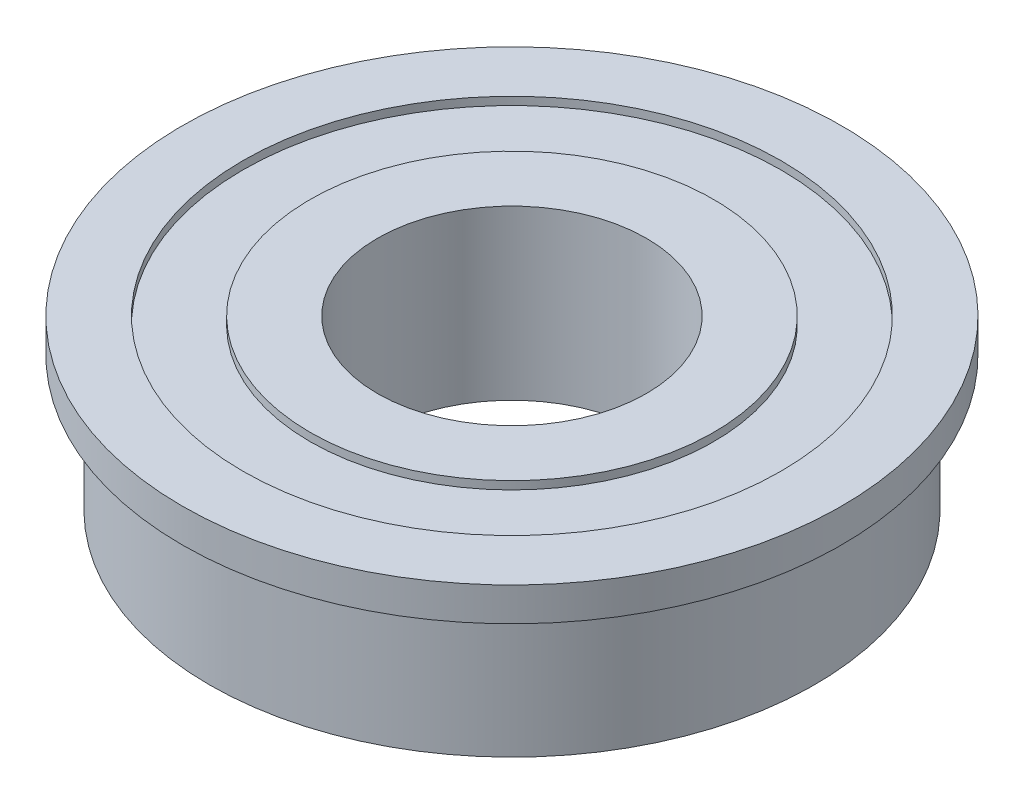
SolidWorks part; units mm, degrees
ref_plane "Front Plane" through (0, 0, 0) normal (0, 0, 1) x (1, 0, 0)
ref_plane "Top Plane" through (0, 0, 0) normal (0, 1, 0) x (1, 0, 0)
ref_plane "Right Plane" through (0, 0, 0) normal (1, 0, 0) x (0, 0, -1)
ref_plane "Plane1" through (0, 0, 0) normal (0, 0, -1) x (-1, 0, 0)
sketch "Sketch1" plane through (0, 0, 0) normal (0, 0, -1) x (-1, 0, 0)
  line L0 (-9.525, 7.5565) -> (-12.7, 7.5565)
  line L1 (-12.7, 7.5565) -> (-12.7, 7.9375)
  line L2 (-12.7, 7.9375) -> (-15.5575, 7.9375)
  line L3 (-15.5575, 7.9375) -> (-15.5575, 6.35)
  line L4 (-15.5575, 6.35) -> (-14.2875, 6.35)
  line L5 (-14.2875, 6.35) -> (-14.2875, 0)
  line L6 (-14.2875, 0) -> (-6.35, 0)
  line L7 (-6.35, 0) -> (-6.35, 7.9375)
  line L8 (-6.35, 7.9375) -> (-9.525, 7.9375)
  line L9 (-9.525, 7.9375) -> (-9.525, 7.5565)
  line L10 (0, 0) -> (0, 7.9375) construction
revolve "Revolve1" add sketch "Sketch1" angle 360 about L10 reverse direction yes
